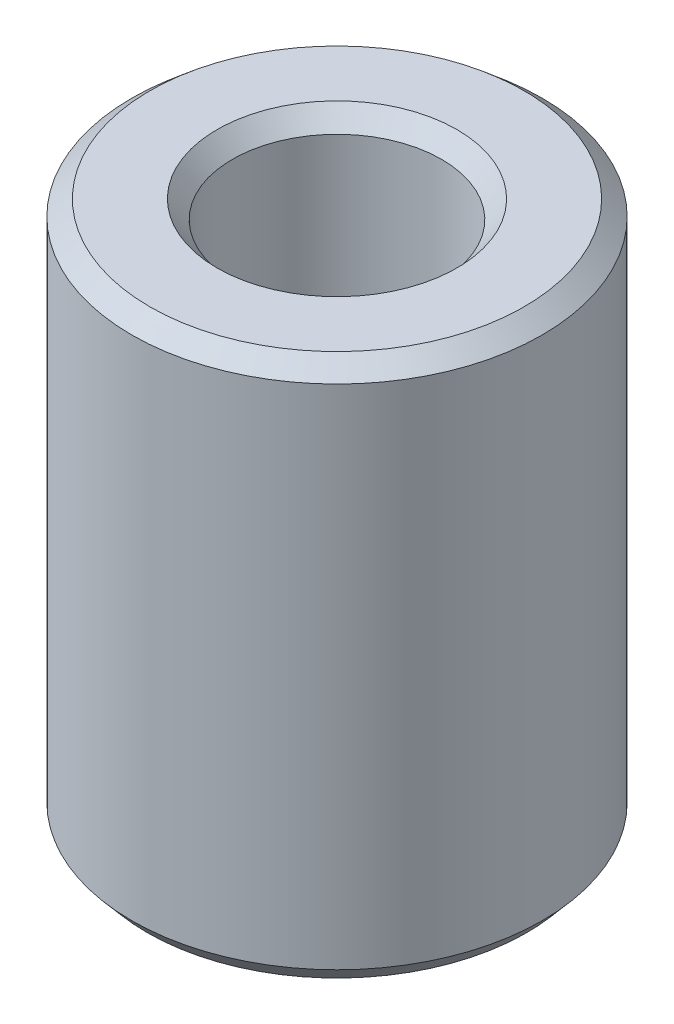
SolidWorks part; units mm, degrees
ref_plane "Front Plane" through (0, 0, 0) normal (0, 0, 1) x (1, 0, 0)
ref_plane "Top Plane" through (0, 0, 0) normal (0, 1, 0) x (1, 0, 0)
ref_plane "Right Plane" through (0, 0, 0) normal (1, 0, 0) x (0, 0, -1)
sketch "Sketch1" plane through (0, 0, 0) normal (0, 1, 0) x (1, 0, 0)
  circle A0 centre (0, 0) radius 12.5
  dimension "SLEEVE_OD" = 25
extrude "Boss-Extrude1" add sketch "Sketch1" along normal blind 32.9397
sketch "Sketch2" plane through (0, 0, 0) normal (0, 1, 0) x (1, 0, 0)
  circle A0 centre (0, 0) radius 6.3696
  dimension "BORE_D" = 12.7391
extrude "Cut-Extrude1" cut sketch "Sketch2" along normal through all
chamfer "Chamfer1" distance 0.9372 angle 49.555 4 edges at (0, 32.9397, 6.3696) (0, 0, 6.3696) (0, 0, 12.5) (0, 32.9397, 12.5) first distance on face at (0, 32.9397, 6.3696) first distance on face at (0, 0, 6.3696) first distance on face at (0, 32.9397, 12.5)
